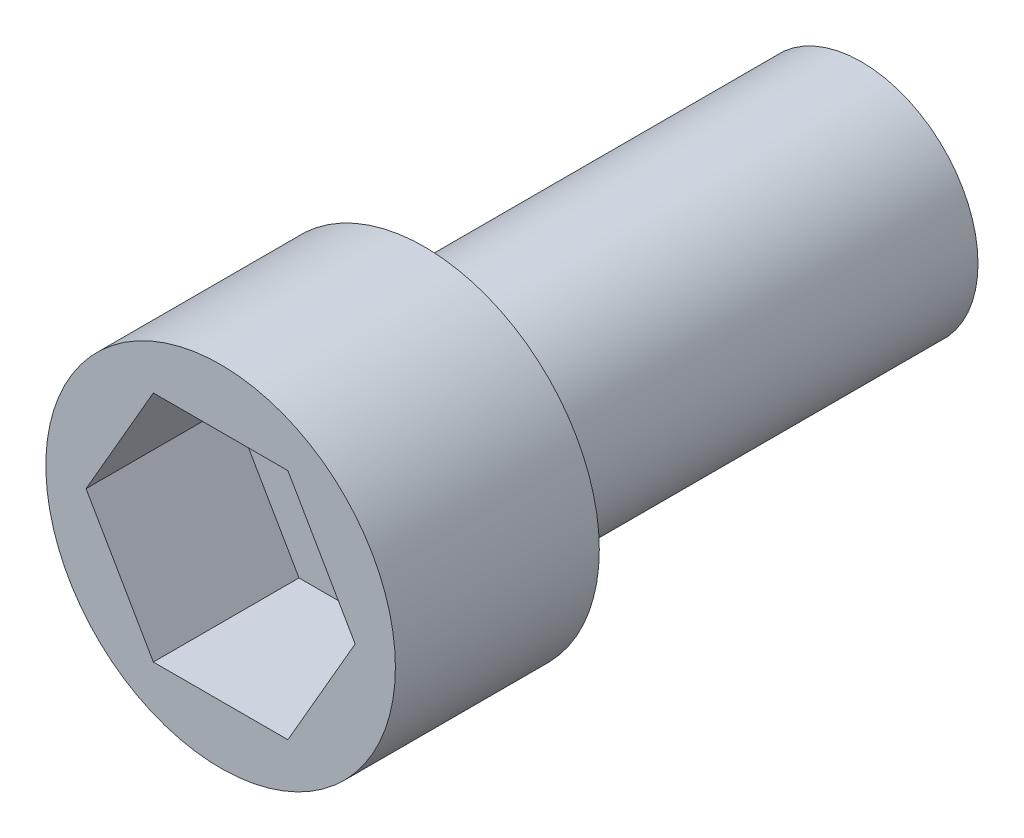
SolidWorks part; units mm, degrees
material "AISI 304"
ref_plane "Front Plane" through (0, 0, 0) normal (0, 0, 1) x (1, 0, 0)
ref_plane "Top Plane" through (0, 0, 0) normal (0, 1, 0) x (1, 0, 0)
ref_plane "Right Plane" through (0, 0, 0) normal (1, 0, 0) x (0, 0, -1)
sketch "Sketch1" plane through (0, 0, 0) normal (0, 0, 1) x (1, 0, 0)
  line L1 (4.6188, 0) -> (2.3094, 4)
  line L2 (2.3094, 4) -> (-2.3094, 4)
  line L3 (-2.3094, 4) -> (-4.6188, 0)
  line L4 (-4.6188, 0) -> (-2.3094, -4)
  line L5 (-2.3094, -4) -> (2.3094, -4)
  line L6 (2.3094, -4) -> (4.6188, 0)
  circle A0 centre (0, 0) radius 6
  circle A1 centre (0, 0) radius 4
  circle A2 centre (0, 0) radius 4 construction
  point P4 (0, 0)
  dimension "D1" = 12
  dimension "D2" = 8
  dimension "D3" = 8
extrude "Boss-Extrude1" add sketch "Sketch1" against normal blind 7 contours A0
extrude "Boss-Extrude2" add sketch "Sketch1<3>" against normal blind 22 contours A1
sketch "Sketch1<3>" plane through (0, 0, 0) normal (0, 0, 1) x (1, 0, 0) same geometry as "Sketch1"
extrude "Cut-Extrude1" cut sketch "Sketch1<4>" against normal blind 5 contours L2 L3 L4 L5 L6 L1
sketch "Sketch1<4>" plane through (0, 0, 0) normal (0, 0, 1) x (1, 0, 0) same geometry as "Sketch1"
